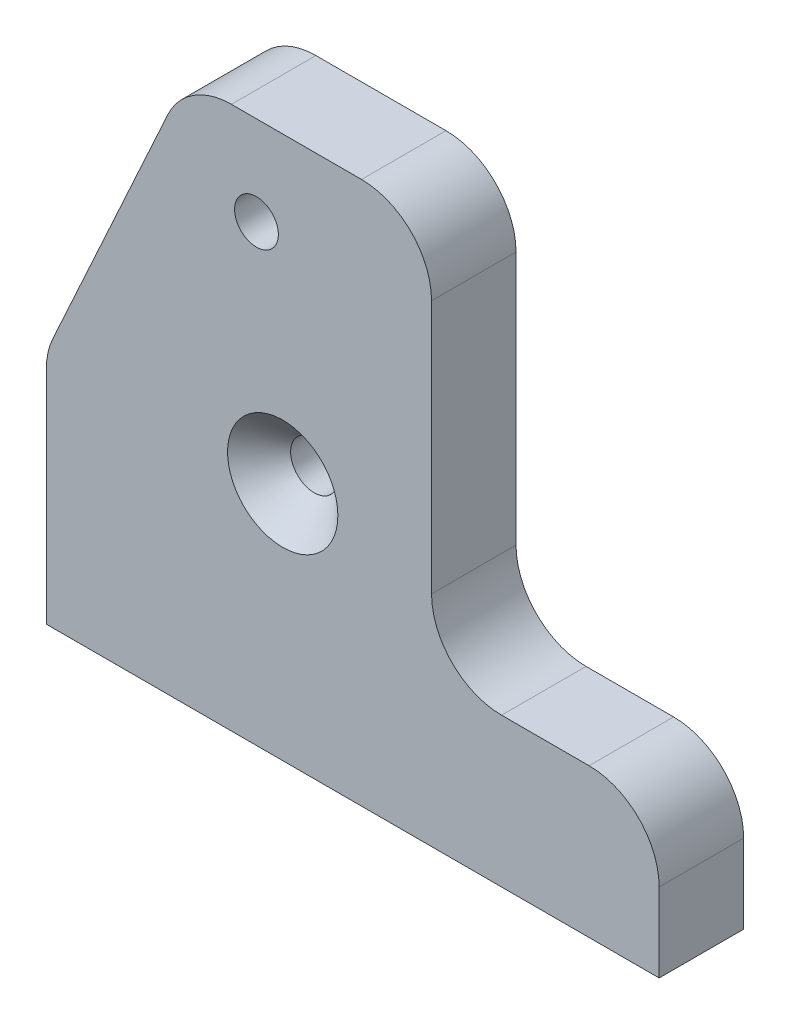
SolidWorks part; units mm, degrees
material "6061 Alloy"
ref_plane "Front" through (0, 0, 0) normal (0, 0, 1) x (1, 0, 0)
ref_plane "Top" through (0, 0, 0) normal (0, 1, 0) x (1, 0, 0)
ref_plane "Right" through (0, 0, 0) normal (1, 0, 0) x (0, 0, -1)
sketch "Sketch1" plane through (0, 0, 0) normal (0, 0, 1) x (1, 0, 0)
  line L0 (0, 0) -> (0, 13.5)
  line L9 (35, 0) -> (0, 0)
  line L15 (8, 31) -> (22, 31)
  line L16 (22, 31) -> (22, 8.5)
  line L17 (22, 8.5) -> (35, 8.5)
  line L18 (35, 8.5) -> (35, 0)
  line L22 (8, 31) -> (0, 13.5)
  dimension "D3" = 13.5
  dimension "D1" = 35
  dimension "D2" = 13
  dimension "D4" = 14
  dimension "D5" = 31
  dimension "D6" = 8.5
extrude "Boss-Extrude1" add sketch "Sketch1" along normal blind 4.826 contours L9 region at (14.4839, 12.8428, 0)
hole_wizard "M3x0.5 Tapped Hole2" positions "Sketch13" profile "Sketch14" tap size "M3x0.5" standard "ANSI Metric" end condition through all
sketch "Sketch13" plane through (0, 0, 4.826) normal (0, 0, 1) x (1, 0, 0)
  line L2 (35, 0) -> (0, 0) construction
  point P5 (12, 25.9)
  dimension "D1" = 25.9
  dimension "D2" = 12
sketch "Sketch14" plane through (12, 25.9, 4.826) normal (1, 0, 0) x (0, -1, 0)
  line L0 (0, 0) -> (0, 4.826)
  line L1 (0, 4.826) -> (1.25, 4.826)
  line L2 (1.25, 4.826) -> (1.25, 0)
  line L5 (1.25, 0) -> (0, 0)
  line L11 (0, -6.35) -> (0, 107.95) construction
  dimension "Thru Tap Drill Dia." = 2.5
  dimension "Thru Tap Drill Depth" = 4.826
cosmetic thread "Hole Thread1" parameters "D2"=3
sketch "Sketch16" plane through (0, 0, 0) normal (0, -1, 0) x (1, 0, 0)
  line L0 (0, 4.826) -> (0, 0) construction
  line L3 (0, 2.413) -> (42.6944, 2.413) construction
  point P0 (28.73, 2.413)
  point P1 (16.73, 2.413)
  dimension "D1" = 16.73
  dimension "D2" = 12
hole_wizard "M3x0.5 Tapped Hole3" positions "Sketch17" profile "Sketch18" tap size "M3x0.5" standard "ANSI Metric"
sketch "Sketch17" plane through (0, 0, 0) normal (0, -1, 0) x (-1, 0, 0)
  point P0 (-16.73, -2.413)
  point P3 (-28.73, -2.413)
sketch "Sketch18" plane through (16.73, 0, 2.413) normal (1, 0, 0) x (0, 0, -1)
  line L0 (0, 0) -> (0, 5.7511)
  line L1 (0, 5.7511) -> (1.25, 5)
  line L2 (1.25, 5) -> (1.25, 0)
  line L5 (1.25, 0) -> (0, 0)
  line L10 (0, 5.7511) -> (-1.25, 5) construction
  line L11 (0, -6.35) -> (0, 107.95) construction
  dimension "Tap Drill Dia." = 2.5
  dimension "Tap Drill Depth" = 5
  dimension "Drill Angle" = 118
chamfer "Chamfer1" [suppressed] distance 13 distance2 10
fillet "Fillet2" radius 4 5 edges at (35, 8.5, 2.413) (22, 8.5, 2.413) (22, 31, 2.413) (0, 13.5, 2.413) (8, 31, 2.413)
sketch "Sketch19" plane through (0, 0, 4.826) normal (0, 0, 1) x (1, 0, 0)
  line L0 (12, 25.9) -> (12, 13.7)
  line L1 (12, 13.7) -> (13.5, 13.7)
  circle A0 centre (13.5, 13.7) radius 1.25
  dimension "D3" = 2.5
  dimension "D1" = 12.2
  dimension "D2" = 1.5
extrude "Cut-Extrude1" cut sketch "Sketch19" against normal blind 10 contours A0 region at (13.5, 12.4854, 4.826)
hole_wizard "CSK for M3 Flat Head Machine Screw1" positions "Sketch20" profile "Sketch22" countersink size "M3" standard "ANSI Metric" end condition through all
sketch "Sketch20" plane through (0, 0, 4.826) normal (0, 0, 1) x (1, 0, 0)
  point P0 (13.5, 13.7)
sketch "Sketch22" plane through (13.5, 13.7, 4.826) normal (1, 0, 0) x (0, -1, 0)
  line L0 (0, 0) -> (0, 4.826)
  line L1 (0, 4.826) -> (1.35, 4.826)
  line L2 (1.35, 4.826) -> (1.35, 1.8)
  line L3 (1.35, 1.8) -> (3.15, 0)
  line L5 (3.15, 0) -> (0, 0)
  line L6 (-1.35, 1.8) -> (-3.15, 0) construction
  line L11 (0, -6.35) -> (0, 107.95) construction
  dimension "Thru Hole Dia." = 2.7
  dimension "Thru Hole Depth" = 4.826
  dimension "Near C'Sink Dia." = 6.3
  dimension "Near C'Sink Angle" = 90
